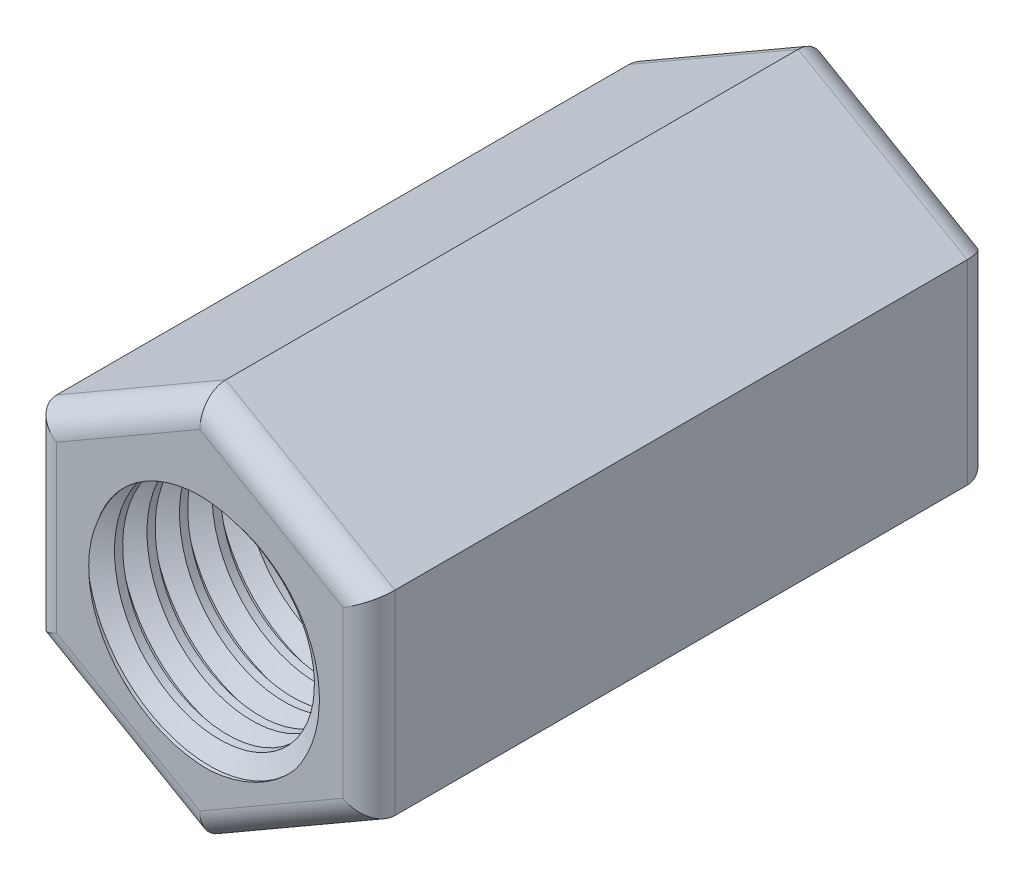
SolidWorks part; units mm, degrees
ref_plane "Спереди" through (0, 0, 0) normal (0, 0, 1) x (1, 0, 0)
ref_plane "Сверху" through (0, 0, 0) normal (0, 1, 0) x (1, 0, 0)
ref_plane "Справа" through (0, 0, 0) normal (1, 0, 0) x (0, 0, -1)
sketch "Эскиз1" plane through (0, 0, 0) normal (0, 0, 1) x (1, 0, 0)
  line L1 (0, -7.5056) -> (6.5, -3.7528)
  line L2 (6.5, -3.7528) -> (6.5, 3.7528)
  line L3 (6.5, 3.7528) -> (0, 7.5056)
  line L4 (0, 7.5056) -> (-6.5, 3.7528)
  line L5 (-6.5, 3.7528) -> (-6.5, -3.7528)
  line L6 (-6.5, -3.7528) -> (0, -7.5056)
  circle A0 centre (0, 0) radius 6.5 construction
  point P1 (0, 0)
  dimension "D1" = 13
extrude "Бобышка-Вытянуть1" add sketch "Эскиз1" along normal blind 24
sketch "Эскиз2" [suppressed] plane through (0, 0, 0) normal (0, 0, -1) x (-1, 0, 0)
  circle A0 centre (0, 0) radius 3.375
  point P4 (0, 0)
  dimension "D1" = 6.75
hole_wizard "Сверло под метчик  спиральное M81" positions "Эскиз4" profile "Эскиз5" hole size "M8x1.25" standard "DIN" end condition through all
sketch "Эскиз4" plane through (0, 0, 0) normal (0, 0, -1) x (-1, 0, 0)
  point P0 (0, 0)
sketch "Эскиз5" plane through (0, 0, 0) normal (1, 0, 0) x (0, 1, 0)
  line L0 (0, 0) -> (0, 24)
  line L1 (0, 24) -> (4.15, 24)
  line L2 (4.15, 24) -> (4.15, 0)
  line L5 (4.15, 0) -> (0, 0)
  line L11 (0, -6.35) -> (0, 107.95) construction
  dimension "Диаметр сквозного отверстия" = 8.3
  dimension "Глубина сквозного отверстия" = 24
thread "Резьба1" pitch 1.25 start angle 0, offset 0, length 0, pitch 1.25, diameter 8.3
ref_plane "Плоскость1" through (4.15, 0, 0) normal (0, -1, 0) x (1, 0, 0)
sketch "Профиль резьбы1" plane through (4.15, 0, 0) normal (0, -1, 0) x (1, 0, 0)
  line L0 (0, 0) -> (0, 1.25) construction
  line L1 (0, 0) -> (0.6766, 0.3906)
  line L2 (0.6766, 0.3906) -> (0.6766, 0.5469)
  line L3 (0.6766, 0.5469) -> (0, 0.9375)
  line L4 (0.6766, 0.4687) -> (0, 0.4687) construction
  line L11 (0, 0) -> (0, 0.9375)
  point P2 (0, 0)
  dimension "Pitch" = 1.25
  dimension "Profile_Angle" = 60
  dimension "Profile_Land" = 0.1562
  dimension "Profile_Height" = 0.6766
fillet "Скругление1" radius 1 12 edges at (3.25, 5.6292, 24) (6.5, 0, 24) (-3.25, 5.6292, 24) (-6.5, 0, 24) (3.25, -5.6292, 24) (-3.25, -5.6292, 24) (-6.5, 0, 0) (-3.25, -5.6292, 0) (3.25, -5.6292, 0) (6.5, 0, 0) (3.25, 5.6292, 0) (-3.25, 5.6292, 0)
